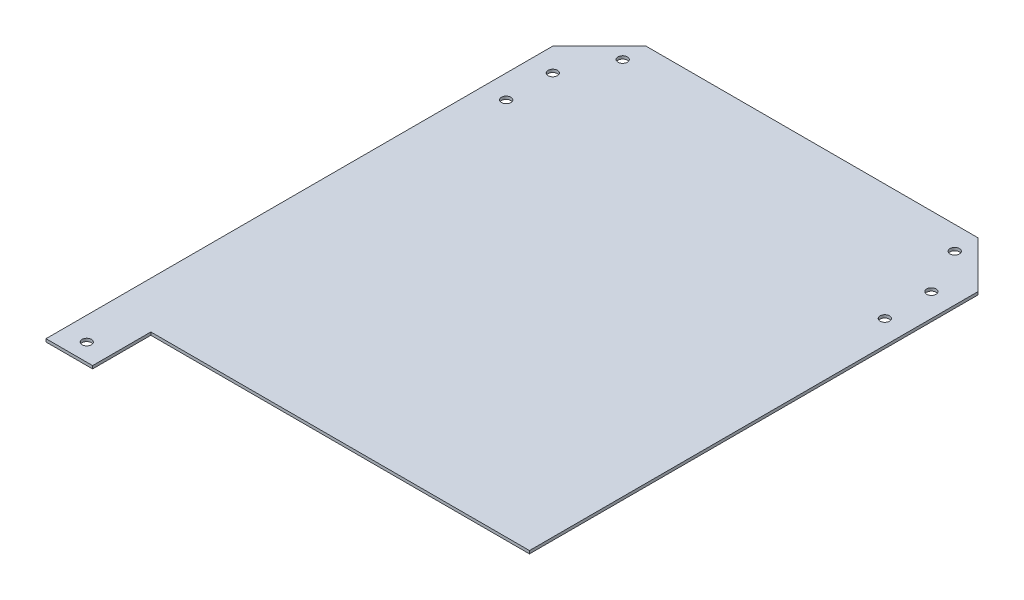
SolidWorks part; units mm, degrees
ref_plane "Front Plane" through (0, 0, 0) normal (0, 0, 1) x (1, 0, 0)
ref_plane "Top Plane" through (0, 0, 0) normal (0, 1, 0) x (1, 0, 0)
ref_plane "Right Plane" through (0, 0, 0) normal (1, 0, 0) x (0, 0, -1)
sketch "Sketch3" plane through (0, 0, 0) normal (0, 1, 0) x (1, 0, 0)
  line L2 (-96.1565, -35.3715) -> (-96.1565, 240.8535)
  line L6 (135.6185, -3.6215) -> (135.6185, 240.8535)
  line L7 (110.2185, 266.2535) -> (-70.7565, 266.2535)
  line L12 (-96.1565, 240.8535) -> (-70.7565, 266.2535)
  line L13 (135.6185, 240.8535) -> (110.2185, 266.2535)
  line L14 (-70.7565, -3.6215) -> (-70.7565, -35.3715)
  line L15 (-70.7565, -394.1465) -> (-70.7565, 240.8535) construction
  line L16 (-70.7565, -3.6215) -> (135.6185, -3.6215)
  line L17 (-70.7565, -35.3715) -> (-96.1565, -35.3715)
extrude "Boss-Extrude1" add sketch "Sketch3" along normal blind 1.5875
hole_wizard "#10 Clearance Hole1" positions "Sketch11" profile "Sketch12" hole size "#10" standard "ANSI Inch" end condition through all
sketch "Sketch11" plane through (0, 1.5875, 0) normal (0, 1, 0) x (1, 0, 0)
  point P0 (-83.4565, -25.8465)
  point P3 (-83.4565, 202.7535)
  point P6 (-83.4565, 228.1535)
  point P9 (-70.7565, 253.5535)
  point P12 (122.9185, 202.7535)
  point P15 (122.9185, 228.1535)
  point P18 (110.2185, 253.5535)
sketch "Sketch12" plane through (-83.4565, 1.5875, 25.8465) normal (1, 0, 0) x (0, 0, 1)
  line L0 (0, 0) -> (0, 1.5875)
  line L1 (0, 1.5875) -> (2.5527, 1.5875)
  line L2 (2.5527, 1.5875) -> (2.5527, 0)
  line L5 (2.5527, 0) -> (0, 0)
  line L11 (0, -6.35) -> (0, 107.95) construction
  dimension "Thru Hole Dia." = 5.1054
  dimension "Thru Hole Depth" = 1.5875
